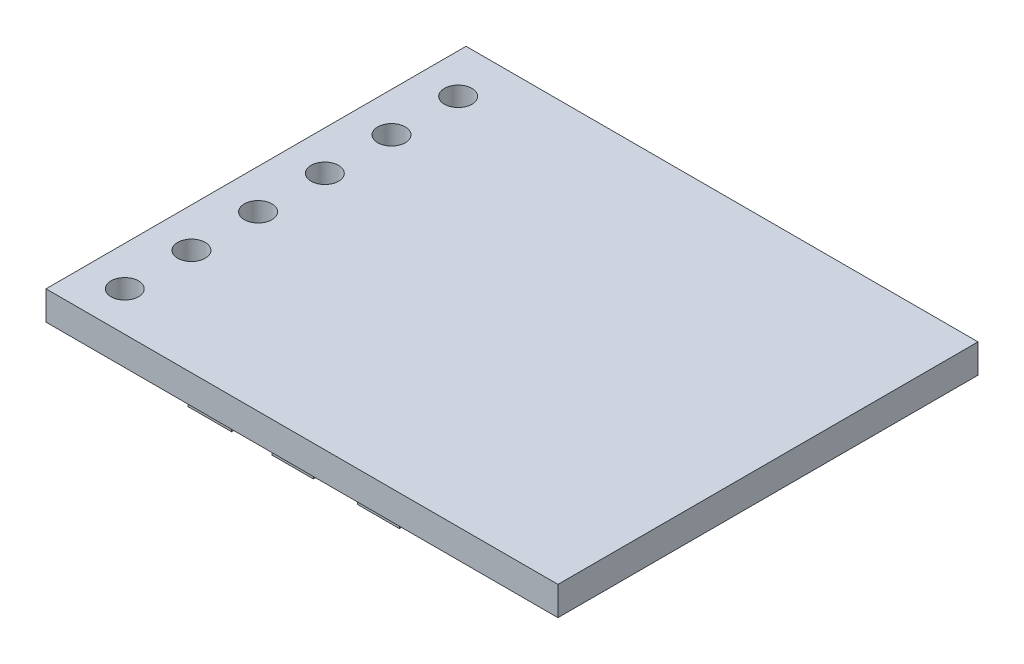
SolidWorks part; units mm, degrees
ref_plane "Front Plane" through (0, 0, 0) normal (0, 0, 1) x (1, 0, 0)
ref_plane "Top Plane" through (0, 0, 0) normal (0, 1, 0) x (1, 0, 0)
ref_plane "Right Plane" through (0, 0, 0) normal (1, 0, 0) x (0, 0, -1)
sketch "Sketch1" plane through (0, 0, 0) normal (0, 1, 0) x (1, 0, 0)
  line L1 (-9.75, 8) -> (9.75, 8)
  line L2 (-9.75, 8) -> (-9.75, -8)
  line L3 (-9.75, -8) -> (9.75, -8)
  line L4 (9.75, 8) -> (9.75, -8)
  line L5 (-9.75, 8) -> (9.75, -8) construction
  line L6 (-9.75, -8) -> (9.75, 8) construction
  point P0 (0, 0)
  dimension "D1" = 19.5
  dimension "D2" = 16
extrude "PCB" add sketch "Sketch1" along normal blind 1.1
sketch "Sketch2" plane through (0, 1.1, 0) normal (0, 1, 0) x (1, 0, 0)
  line L0 (-8.25, 8) -> (-8.25, -8) construction
  line L1 (9.75, 8) -> (-9.75, 8) construction
  line L2 (-9.75, -8) -> (9.75, -8) construction
  line L3 (-9.75, 8) -> (-9.75, -8) construction
  circle A0 centre (-8.25, -6.5) radius 0.525
  circle A1 centre (-8.25, -3.96) radius 0.525
  circle A2 centre (-8.25, -1.42) radius 0.525
  circle A3 centre (-8.25, 1.12) radius 0.525
  circle A4 centre (-8.25, 3.66) radius 0.525
  circle A5 centre (-8.25, 6.2) radius 0.525
  dimension "D1" = 1.05
  dimension "D5" = 2.54
  dimension "D2" = 1.5
  dimension "D3" = 1.5
  dimension "D4" = 6
extrude "Holes" cut sketch "Sketch2" against normal up to next
sketch "Sketch3" plane through (0, 0, 0) normal (0, -1, 0) x (1, 0, 0)
  line L1 (-2.8189, 4.1517) -> (4.1517, 4.1517)
  line L2 (-2.8189, 4.1517) -> (-2.8189, -2.8955)
  line L3 (-2.8189, -2.8955) -> (4.1517, -2.8955)
  line L4 (4.1517, 4.1517) -> (4.1517, -2.8955)
  line L5 (-6.0514, -4.259) -> (-2.8189, -4.259)
  line L6 (-6.0514, -4.259) -> (-6.0514, -6.1127)
  line L7 (-6.0514, -6.1127) -> (-2.8189, -6.1127)
  line L8 (-2.8189, -4.259) -> (-2.8189, -6.1127)
  line L9 (-1.8384, -4.9637) -> (-0.2298, -4.9637)
  line L10 (-1.8384, -4.9637) -> (-1.8384, -5.6378)
  line L11 (-1.8384, -5.6378) -> (-0.2298, -5.6378)
  line L12 (-0.2298, -4.9637) -> (-0.2298, -5.6378)
  line L13 (-1.8384, -5.8829) -> (-0.2298, -5.8829)
  line L14 (-1.8384, -5.8829) -> (-1.8384, -6.6489)
  line L15 (-1.8384, -6.6489) -> (-0.2298, -6.6489)
  line L16 (-0.2298, -5.8829) -> (-0.2298, -6.6489)
  line L17 (0.812, -5.4999) -> (3.9526, -5.4999)
  line L18 (0.812, -5.4999) -> (0.812, -6.9706)
  line L19 (0.812, -6.9706) -> (3.9526, -6.9706)
  line L20 (3.9526, -5.4999) -> (3.9526, -6.9706)
  line L21 (4.4735, 6.6489) -> (5.4233, 6.6489)
  line L22 (4.4735, 6.6489) -> (4.4735, 5.2854)
  line L23 (4.4735, 5.2854) -> (5.4233, 5.2854)
  line L24 (5.4233, 6.6489) -> (5.4233, 5.2854)
  line L25 (5.8063, 6.6489) -> (6.7255, 6.6489)
  line L26 (5.8063, 6.6489) -> (5.8063, 5.2854)
  line L27 (5.8063, 5.2854) -> (6.7255, 5.2854)
  line L28 (6.7255, 6.6489) -> (6.7255, 5.2854)
  line L29 (2.7423, 7.0319) -> (1.149, 7.0319)
  line L30 (2.7423, 7.0319) -> (2.7423, 6.2046)
  line L31 (2.7423, 6.2046) -> (1.149, 6.2046)
  line L32 (1.149, 7.0319) -> (1.149, 6.2046)
  line L33 (-0.5362, 7.0319) -> (-2.1142, 7.0319)
  line L34 (-0.5362, 7.0319) -> (-0.5362, 6.2046)
  line L35 (-0.5362, 6.2046) -> (-2.1142, 6.2046)
  line L36 (-2.1142, 7.0319) -> (-2.1142, 6.2046)
  line L37 (-3.6462, 7.0319) -> (-5.3161, 7.0319)
  line L38 (-3.6462, 7.0319) -> (-3.6462, 6.2046)
  line L39 (-3.6462, 6.2046) -> (-5.3161, 6.2046)
  line L40 (-5.3161, 7.0319) -> (-5.3161, 6.2046)
  line L41 (4.4735, -4.9637) -> (5.5152, -4.9637)
  line L42 (4.4735, -4.9637) -> (4.4735, -6.4804)
  line L43 (4.4735, -6.4804) -> (5.5152, -6.4804)
  line L44 (5.5152, -4.9637) -> (5.5152, -6.4804)
  line L45 (5.9442, -4.9637) -> (6.8787, -4.9637)
  line L46 (5.9442, -4.9637) -> (5.9442, -6.4804)
  line L47 (5.9442, -6.4804) -> (6.8787, -6.4804)
  line L48 (6.8787, -4.9637) -> (6.8787, -6.4804)
extrude "Bottom components" add sketch "Sketch3" along normal blind 1.05
